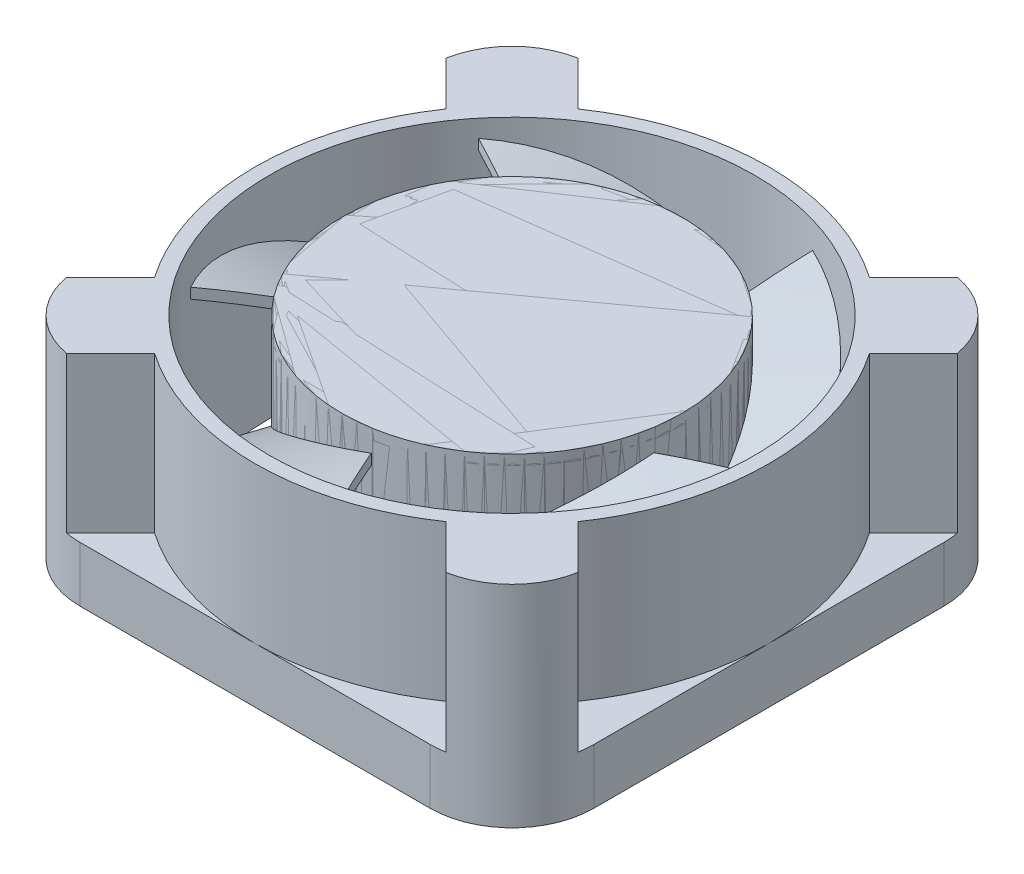
SolidWorks part; units mm, degrees
ref_plane "Ebene vorne" through (0, 0, 0) normal (0, 0, 1) x (1, 0, 0)
ref_plane "Ebene oben" through (0, 0, 0) normal (0, 1, 0) x (1, 0, 0)
ref_plane "Ebene rechts" through (0, 0, 0) normal (1, 0, 0) x (0, 0, -1)
ref_axis "Achse1" through (0, -9.5275, 0) along (0, 1, 0)
sketch "Skizze9" plane through (0, 0, 0) normal (0, 1, 0) x (1, 0, 0)
  line L0 (0, 12.55) -> (0, -12.55) construction
  line L1 (-12.55, 12.55) -> (12.55, 12.55)
  line L2 (-12.55, 12.55) -> (-12.55, -12.55)
  line L3 (-12.55, -12.55) -> (12.55, -12.55)
  line L4 (12.55, 12.55) -> (12.55, -12.55)
  line L5 (-12.55, 12.55) -> (12.55, -12.55) construction
  line L6 (-12.55, 0) -> (-12.55, 9.3327)
  line L7 (-12.55, 9.3327) -> (-10.3358, 7.1185)
  line L8 (12.55, 12.55) -> (-12.55, -12.55) construction
  line L9 (-12.55, 0) -> (12.55, 0) construction
  line L10 (-7.1185, 10.3358) -> (-9.3327, 12.55)
  line L11 (7.1185, 10.3358) -> (9.3327, 12.55)
  line L12 (12.55, 9.3327) -> (10.3358, 7.1185)
  line L13 (-12.55, -9.3327) -> (-10.3358, -7.1185)
  line L14 (-7.1185, -10.3358) -> (-9.3327, -12.55)
  line L15 (12.55, -9.3327) -> (10.3358, -7.1185)
  line L16 (7.1185, -10.3358) -> (9.3327, -12.55)
  line L17 (-9.0564, 7.6422) -> (-6.3196, 4.9054)
  line L18 (-7.6422, 9.0564) -> (-4.9054, 6.3196)
  line L19 (7.6422, 9.0564) -> (4.9054, 6.3196)
  line L20 (9.0564, 7.6422) -> (6.3196, 4.9054)
  line L21 (-9.0564, -7.6422) -> (-6.3196, -4.9054)
  line L22 (-7.6422, -9.0564) -> (-4.9054, -6.3196)
  line L23 (7.6422, -9.0564) -> (4.9054, -6.3196)
  line L24 (9.0564, -7.6422) -> (6.3196, -4.9054)
  circle A0 centre (0, 0) radius 12.55
  circle A1 centre (0, 0) radius 11.85
  circle A2 centre (0, 0) radius 8
  circle A3 centre (0, 0) radius 14.1421 construction
  point P45 (-10, 10)
  point P46 (10, 10)
  point P47 (10, -10)
  point P48 (-10, -10)
  dimension "D3" = 0.7
  dimension "D5" = 16
  dimension "D6" = 20
  dimension "D1" = 25.1
  dimension "D2" = 4.55
  dimension "D4" = 2
extrude "Aufsatz-Linear austragen5" add sketch "Skizze9" along normal blind 2.7 separate body contours A1 | A2 L17 A1 L21 | A2 L22 A1 L23 | A2 L24 A1 L20 | L3 L4 L1 L2 region at (-9.2966, 0, 0) region at (0, 0, -9.2966) region at (0, 0, 9.2966) region at (9.2966, 0, 0)
extrude "Aufsatz-Linear austragen6" add sketch "Skizze9<4>" along normal blind 10.3 contours A0 A1 | A0 L10 L1 L2 L7 | A0 L12 L4 L1 L11 | A0 L16 L3 L4 L15 | A0 L13 L2 L3 L14 region at (-10.3221, 0, -10.3221) region at (3.622, 0, -11.6447) region at (10.3221, 0, -10.3221) region at (-10.3221, 0, 10.3221) region at (10.3221, 0, 10.3221)
sketch "Skizze9<4>" plane through (0, 0, 0) normal (0, 1, 0) x (1, 0, 0) same geometry as "Skizze9"
fillet "Verrundung7" radius 4 4 edges at (-12.55, 5.15, -12.55) (12.55, 5.15, -12.55) (12.55, 5.15, 12.55) (-12.55, 5.15, 12.55)
sketch "Skizze10" plane through (0, 2.7, 0) normal (0, 1, 0) x (1, 0, 0)
  circle A0 centre (0, 0) radius 8.3
  dimension "D1" = 16.6
extrude "Aufsatz-Linear austragen7" add sketch "Skizze10" along normal up to surface (7.6 mm away) from offset 0.5 separate body up to face at (0, 10.3, 11.85)
ref_plane "Ebene3" through (-20, 0, 0) normal (1, 0, 0) x (0, 0, -1)
sketch "Skizze12" plane through (-20, 0, 0) normal (1, 0, 0) x (0, 0, -1)
  line L0 (8.3, 10.3) -> (-8.3, 10.3) construction
  line L1 (-6.1557, 9.8) -> (-6.25, 9.309)
  line L2 (6.25, 3.5688) -> (5.9124, 3.2)
  line L3 (-8.3, 3.2) -> (8.3, 3.2) construction
  line L4 (0, 10.3) -> (0, 16.36) construction
  line L5 (6.25, 3.5688) -> (0, 3.5688) construction
  line L6 (0, 9.309) -> (-6.25, 9.309) construction
  line L7 (7.1185, 10.3) -> (-7.1185, 10.3) construction
  arc A0 (6.25, 3.5688) -> (-6.1557, 9.8) centre (-10.9662, -15.2421) ccw
  arc A1 (-6.25, 9.309) -> (5.9124, 3.2) centre (-10.9662, -15.2421) cw
  dimension "D1" = 0.5
  dimension "D3" = 25
  dimension "D2" = 12.5
  dimension "D4" = 0.5
extrude "Aufsatz-Linear austragen8" add sketch "Skizze12" along normal up to surface (14.1748 mm away) up to face at (0, 3.2, 8.3)
sketch "Skizze13" plane through (0, 10.3, 0) normal (0, 1, 0) x (1, 0, 0)
  circle A0 centre (0, 0) radius 11.35
  circle A1 centre (0, 0) radius 11.85 construction
  dimension "D1" = 0.5
extrude "Schnitt-Linear austragen4" cut sketch "Skizze13" against normal up to surface (7.6 mm away) flip side to cut up to face at (12.1195, 2.7, 6.2765)
sketch "Skizze15" plane through (0, 10.3, 0) normal (0, 1, 0) x (1, 0, 0)
  line L0 (-9.4742, 6.25) -> (-6.7735, 4.7968)
  line L1 (-9.5357, -6.1557) -> (-7.3842, -3.7899)
  line L2 (0, 0) -> (-11.3499, 0.0563) construction
  circle A0 centre (0, 0) radius 8.3 construction
  arc A1 (-5.4615, 6.25) -> (-5.5676, -6.1557) centre (0, 0) ccw construction
  arc A2 (-9.4742, 6.25) -> (-9.5357, -6.1557) centre (0, 0) ccw construction
  arc A3 (-9.4742, 6.25) -> (-9.5357, -6.1557) centre (0, 0) ccw
  arc A4 (-6.7735, 4.7968) -> (-7.3842, -3.7899) centre (0, 0) cw
  dimension "D1" = 76
  dimension "D2" = 28
extrude "Schnitt-Linear austragen7" cut sketch "Skizze15" against normal up to surface (7.6 mm away) flip side to cut up to face at (12.1195, 2.7, 6.2765)
pattern_circular "Kreismuster2" count 5 over 360 about axis through (0, -9.5275, 0) along (0, 1, 0) of bodies 120 113
fillet "Verrundung8" radius 0.5 1 edges at (0, 10.3, 8.3)
sketch "Skizze14" plane through (0, -17.3, 0) normal (0, 1, 0) x (1, 0, 0)
  line L1 (19.75, -5.8) -> (23.15, -5.8)
  line L2 (19.75, -5.8) -> (19.75, -11)
  line L3 (19.75, -11) -> (23.15, -11)
  line L4 (23.15, -5.8) -> (23.15, -11)
extrude "Aufsatz-Linear austragen9" [suppressed] add sketch "Skizze14" along normal offset from surface (16.65 mm away) 20.9 separate body
